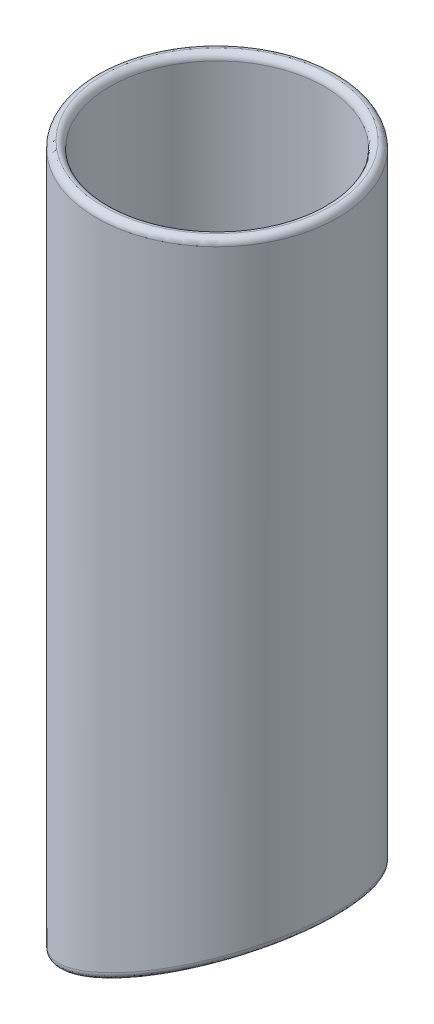
SolidWorks part; units mm, degrees
ref_plane "Front Plane" through (0, 0, 0) normal (0, 0, 1) x (1, 0, 0)
ref_plane "Top Plane" through (0, 0, 0) normal (0, 1, 0) x (1, 0, 0)
ref_plane "Right Plane" through (0, 0, 0) normal (1, 0, 0) x (0, 0, -1)
sketch "Sketch1" plane through (0, 0, 0) normal (0, 0, 1) x (1, 0, 0)
  line L0 (-2.032, 0) -> (-2.032, 14.2344)
  line L1 (-2.032, 14.2344) -> (-4.7625, 15.875)
  line L2 (-4.7625, 15.875) -> (-12.7, 15.875)
  line L3 (-12.7, 15.875) -> (-12.7, 85.725)
  line L4 (-12.7, 85.725) -> (-14.2875, 85.725)
  line L5 (-14.2875, 85.725) -> (-14.2875, 0)
  line L6 (-14.2875, 0) -> (-2.032, 0)
  line L7 (0, 0) -> (0, 85.725) construction
  line L8 (-12.7, 85.725) -> (0, 85.725) construction
  line L9 (-2.032, 0) -> (0, 0) construction
  point P10 (-10.9336, 5.7181)
  point P11 (-12.7, 9.3374)
  dimension "D1" = 59
  dimension "D2" = 4.064
  dimension "D3" = 9.525
  dimension "D4" = 25.4
  dimension "D5" = 1.5875
  dimension "D6" = 69.85
  dimension "D7" = 15.875
revolve "Revolve1" add sketch "Sketch1" angle 360 about L7
sketch "Sketch2" plane through (0, 0, 0) normal (0, 0, 1) x (1, 0, 0)
  line L0 (-14.2875, 0) -> (14.2875, 13.3247)
  line L1 (14.2875, 0) -> (14.2875, 85.725) construction
  line L2 (14.2875, 13.3247) -> (14.2875, 0)
  line L3 (14.2875, 0) -> (-14.2875, 0)
  dimension "D1" = 25
extrude "Cut-Extrude1" cut sketch "Sketch2" against normal through all both and the other way through all
fillet "Fillet1" radius 0.7937 4 edges at (0, 15.875, -12.7) (0, 85.725, -14.2875) (0, 85.725, -12.7) (-14.2875, 0, 0)
